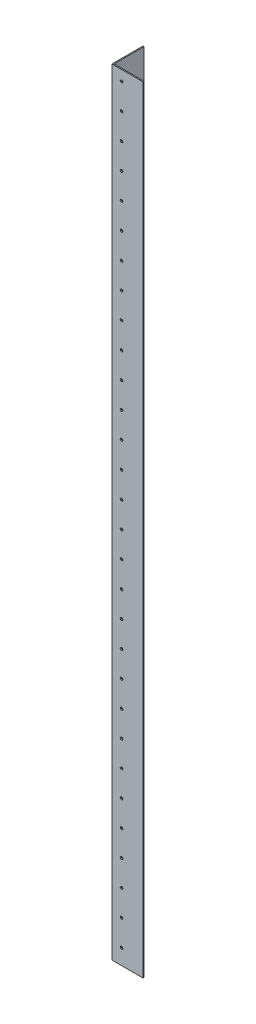
SolidWorks part; units mm, degrees
ref_plane "Спереди" through (0, 0, 0) normal (0, 0, 1) x (1, 0, 0)
ref_plane "Сверху" through (0, 0, 0) normal (0, 1, 0) x (1, 0, 0)
ref_plane "Справа" through (0, 0, 0) normal (1, 0, 0) x (0, 0, -1)
sketch "Эскиз1" plane through (0, 0, 0) normal (0, 1, 0) x (1, 0, 0)
  line L0 (0, 60) -> (0, 0)
  line L1 (0, 0) -> (60, 0)
extrude "Вытянуть-Тонкостенный1" add sketch "Эскиз1" along normal blind 1500 thin thin type one direction reverse wall 2
sketch "Эскиз2" plane through (0, 0, 0) normal (-1, 0, 0) x (0, 0, 1)
  circle A0 centre (-18.5, 30) radius 2.5
  circle A1 centre (-18.5, 80) radius 2.5
  circle A2 centre (-18.5, 130) radius 2.5
  circle A3 centre (-18.5, 180) radius 2.5
  circle A4 centre (-18.5, 230) radius 2.5
  circle A5 centre (-18.5, 280) radius 2.5
  circle A6 centre (-18.5, 330) radius 2.5
  circle A7 centre (-18.5, 380) radius 2.5
  circle A8 centre (-18.5, 430) radius 2.5
  circle A9 centre (-18.5, 480) radius 2.5
  circle A10 centre (-18.5, 530) radius 2.5
  circle A11 centre (-18.5, 580) radius 2.5
  circle A12 centre (-18.5, 630) radius 2.5
  circle A13 centre (-18.5, 680) radius 2.5
  circle A14 centre (-18.5, 730) radius 2.5
  circle A15 centre (-18.5, 780) radius 2.5
  circle A16 centre (-18.5, 830) radius 2.5
  circle A17 centre (-18.5, 880) radius 2.5
  circle A18 centre (-18.5, 930) radius 2.5
  circle A19 centre (-18.5, 980) radius 2.5
  circle A20 centre (-18.5, 1030) radius 2.5
  circle A21 centre (-18.5, 1080) radius 2.5
  circle A22 centre (-18.5, 1130) radius 2.5
  circle A23 centre (-18.5, 1180) radius 2.5
  circle A24 centre (-18.5, 1230) radius 2.5
  circle A25 centre (-18.5, 1280) radius 2.5
  circle A26 centre (-18.5, 1330) radius 2.5
  circle A27 centre (-18.5, 1380) radius 2.5
  circle A28 centre (-18.5, 1430) radius 2.5
  circle A29 centre (-18.5, 1480) radius 2.5
  dimension "D1" = 30
extrude "Вырез-Вытянуть1" cut sketch "Эскиз2" against normal through all
sketch "Эскиз3" plane through (0, 0, 0) normal (0, 0, 1) x (1, 0, 0)
  circle A0 centre (18.5, 30) radius 2.5
  circle A1 centre (18.5, 80) radius 2.5
  circle A2 centre (18.5, 130) radius 2.5
  circle A3 centre (18.5, 180) radius 2.5
  circle A4 centre (18.5, 230) radius 2.5
  circle A5 centre (18.5, 280) radius 2.5
  circle A6 centre (18.5, 330) radius 2.5
  circle A7 centre (18.5, 380) radius 2.5
  circle A8 centre (18.5, 430) radius 2.5
  circle A9 centre (18.5, 480) radius 2.5
  circle A10 centre (18.5, 530) radius 2.5
  circle A11 centre (18.5, 580) radius 2.5
  circle A12 centre (18.5, 630) radius 2.5
  circle A13 centre (18.5, 680) radius 2.5
  circle A14 centre (18.5, 730) radius 2.5
  circle A15 centre (18.5, 780) radius 2.5
  circle A16 centre (18.5, 830) radius 2.5
  circle A17 centre (18.5, 880) radius 2.5
  circle A18 centre (18.5, 930) radius 2.5
  circle A19 centre (18.5, 980) radius 2.5
  circle A20 centre (18.5, 1030) radius 2.5
  circle A21 centre (18.5, 1080) radius 2.5
  circle A22 centre (18.5, 1130) radius 2.5
  circle A23 centre (18.5, 1180) radius 2.5
  circle A24 centre (18.5, 1230) radius 2.5
  circle A25 centre (18.5, 1280) radius 2.5
  circle A26 centre (18.5, 1330) radius 2.5
  circle A27 centre (18.5, 1380) radius 2.5
  circle A28 centre (18.5, 1430) radius 2.5
  circle A29 centre (18.5, 1480) radius 2.5
  dimension "D1" = 30
extrude "Вырез-Вытянуть2" cut sketch "Эскиз3" against normal through all
